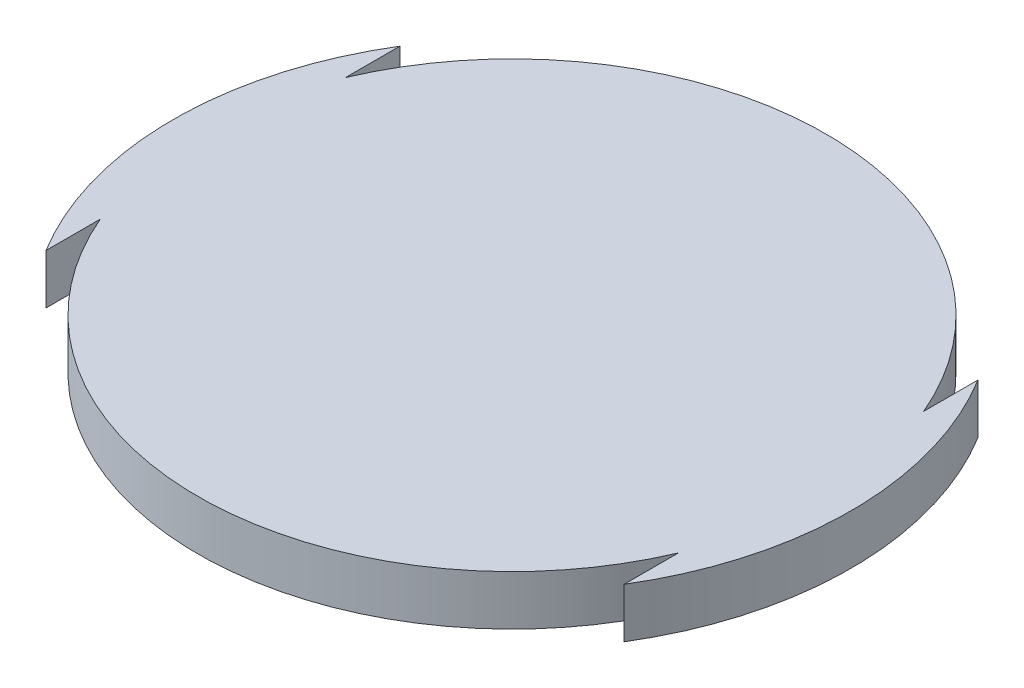
SolidWorks part; units mm, degrees
ref_plane "Front Plane" through (0, 0, 0) normal (0, 0, 1) x (1, 0, 0)
ref_plane "Top Plane" through (0, 0, 0) normal (0, 1, 0) x (1, 0, 0)
ref_plane "Right Plane" through (0, 0, 0) normal (1, 0, 0) x (0, 0, -1)
sketch "Sketch1" plane through (0, 0, 0) normal (0, 1, 0) x (1, 0, 0)
  circle A0 centre (0, 0) radius 68
  dimension "D1" = 136
extrude "Boss-Extrude1" add sketch "Sketch1" along normal blind 10
sketch "Sketch2" plane through (0, 10, 0) normal (0, 1, 0) x (1, 0, 0)
  line L0 (-58, -35.4965) -> (-58, -24.5967)
  line L1 (0, 37.0764) -> (0, -27.4787) construction
  line L2 (58, 35.4965) -> (58, 24.5967)
  line L3 (-58, 24.5967) -> (-58, 35.4965)
  line L4 (58, -24.5967) -> (58, -35.4965)
  arc A0 (-58, -24.5967) -> (58, -24.5967) centre (0, 0) ccw
  arc A1 (-58, -35.4965) -> (58, -35.4965) centre (0, 0) ccw
  circle A2 centre (0, 0) radius 68 construction
  arc A3 (58, 24.5967) -> (-58, 24.5967) centre (0, 0) ccw
  arc A4 (58, 35.4965) -> (-58, 35.4965) centre (0, 0) ccw
  dimension "D1" = 126
  dimension "D2" = 58
  dimension "D3" = 58
extrude "Cut-Extrude1" cut sketch "Sketch2" against normal up to surface (10 mm away) up to face at (0, 0, 68)
